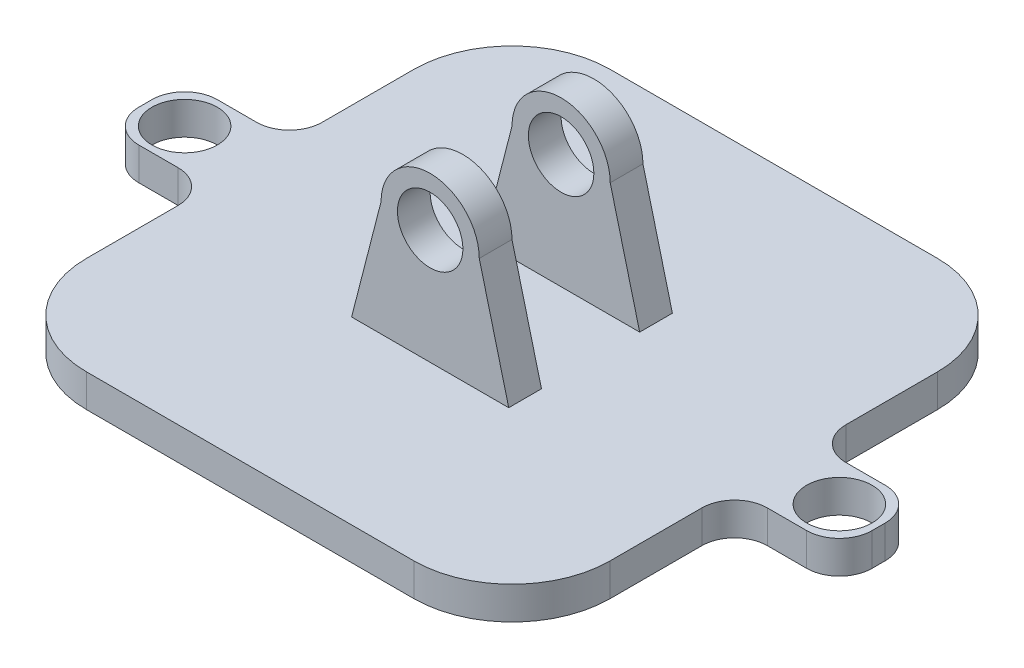
SolidWorks part; units mm, degrees
ref_plane "Front Plane" through (0, 0, 0) normal (0, 0, 1) x (1, 0, 0)
ref_plane "Top Plane" through (0, 0, 0) normal (0, 1, 0) x (1, 0, 0)
ref_plane "Right Plane" through (0, 0, 0) normal (1, 0, 0) x (0, 0, -1)
sketch "Sketch1" plane through (0, 0, 0) normal (0, 1, 0) x (1, 0, 0)
  line L0 (-40, 6) -> (-56, 6)
  line L1 (-25, 40) -> (25, 40)
  line L2 (-40, 25) -> (-40, 6)
  line L3 (-25, -40) -> (25, -40)
  line L4 (40, 25) -> (40, 6)
  line L5 (-40, 40) -> (40, -40) construction
  line L6 (-40, -40) -> (40, 40) construction
  line L7 (-40, -6) -> (-56, -6)
  line L8 (-56, 6) -> (-56, -6)
  line L9 (0, 18.0857) -> (0, -17.603) construction
  line L10 (40, -6) -> (56, -6)
  line L11 (56, 6) -> (56, -6)
  line L12 (40, 6) -> (56, 6)
  line L13 (-40, -6) -> (-40, -25)
  line L14 (40, -6) -> (40, -25)
  arc A0 (25, -40) -> (40, -25) centre (25, -25) ccw
  arc A1 (-40, -25) -> (-25, -40) centre (-25, -25) ccw
  arc A2 (25, 40) -> (40, 25) centre (25, 25) cw
  arc A3 (-25, 40) -> (-40, 25) centre (-25, 25) ccw
  circle A4 centre (-50, 0) radius 5
  circle A5 centre (50, 0) radius 5
  point P0 (0, 0)
  dimension "D3" = 15
  dimension "D4" = 10
  dimension "D1" = 80
  dimension "D2" = 80
  dimension "D5" = 10
  dimension "D6" = 40
  dimension "D7" = 6
  dimension "D8" = 6
  dimension "D9" = 16
extrude "Boss-Extrude1" add sketch "Sketch1" along normal mid plane 5
fillet "Fillet1" radius 5 8 edges at (-40, 0, 6) (-56, 0, 6) (-56, 0, -6) (-40, 0, -6) (40, 0, -6) (56, 0, -6) (56, 0, 6) (40, 0, 6)
sketch "Sketch2" plane through (0, 0, 0) normal (0, 0, 1) x (1, 0, 0)
  line L0 (-7.5, 20) -> (-12, 2.5)
  line L1 (-25, 2.5) -> (25, 2.5) construction
  line L2 (7.5, 20) -> (12, 2.5)
  line L3 (-12, 2.5) -> (12, 2.5)
  line L4 (12, 2.5) -> (12.1865, 2.3361)
  arc A0 (7.5, 20) -> (-7.5, 20) centre (0, 20) ccw
  dimension "D1" = 15
  dimension "D2" = 20
  dimension "D3" = 12
  dimension "D4" = 12
extrude "Boss-Extrude2" add sketch "Sketch2" along normal mid plane 5 from offset 10 contours L2 A0 L0 L3
extrude "Boss-Extrude3" add sketch "Sketch2<6>" along normal mid plane 5 from offset 10 contours L2 A0 L0 L3 region at (0, 13.1696, 0) offset against normal yes
sketch "Sketch2<6>" plane through (0, 0, 0) normal (0, 0, 1) x (1, 0, 0) same geometry as "Sketch2"
sketch "Sketch3" plane through (0, 0, 12.5) normal (0, 0, 1) x (1, 0, 0)
  circle A0 centre (0, 20) radius 5
  dimension "D1" = 10
extrude "Cut-Extrude1" cut sketch "Sketch3" against normal through all
